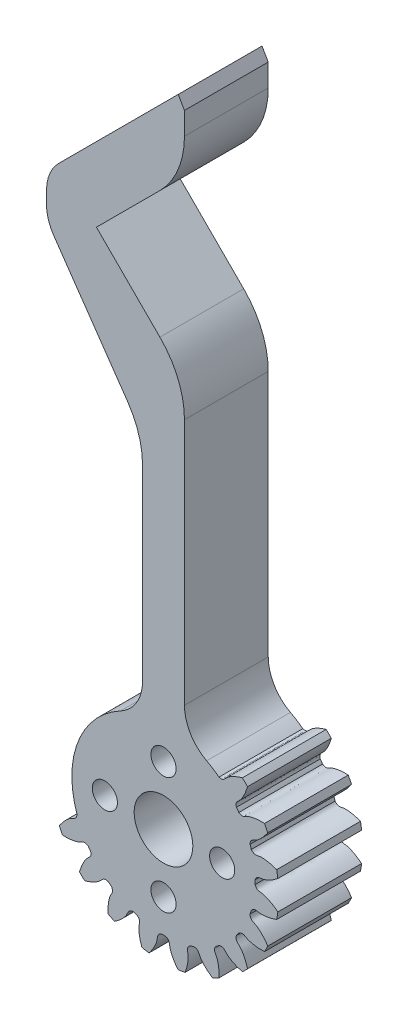
SolidWorks part; units mm, degrees
material "聚脂树脂"
ref_plane "前视基准面" through (0, 0, 0) normal (0, 0, 1) x (1, 0, 0)
ref_plane "上视基准面" through (0, 0, 0) normal (0, 1, 0) x (1, 0, 0)
ref_plane "右视基准面" through (0, 0, 0) normal (1, 0, 0) x (0, 0, -1)
other "Configuration Table"
sketch "草图1" plane through (0, 0, 0) normal (0, 0, 1) x (1, 0, 0)
  circle A0 centre (0, 0) radius 13.75
extrude "凸台-拉伸1" add sketch "草图1" along normal blind 10
ref_axis "基准轴1" through (0, 0, -1.5) along (0, 0, 1)
sketch "草图2" plane through (0, 0, 0) normal (0, 0, 1) x (1, 0, 0)
  line L0 (0, 0) -> (0, 13.75) construction
  circle A0 centre (0, 0) radius 13.75 construction
  arc A1 (0.2416, 10.9348) -> (-0.2416, 10.9348) centre (0, 0) ccw
  arc A2 (3.9764, 15.6228) -> (-3.9764, 15.6228) centre (0, 0) ccw
  spline S0 degree 3 poles (0.2416, 10.9348) (0.764, 11.1168) (0.6964, 11.4839) (0.7661, 11.8375) (0.7736, 11.8719) (0.7829, 11.9108) (0.7941, 11.954) (0.8075, 12.0015) (0.8231, 12.0532) (0.8413, 12.1091) (0.8621, 12.169) (0.8857, 12.2329) (0.9123, 12.3007) (0.9421, 12.3723) (0.9752, 12.4476) (1.0117, 12.5264) (1.0519, 12.6088) (1.0959, 12.6945) (1.1438, 12.7834) (1.1957, 12.8755) (1.2519, 12.9705) (1.3125, 13.0684) (1.3775, 13.1691) (1.4472, 13.2723) (1.5216, 13.3779) (1.601, 13.4858) (1.6853, 13.5958) (1.7747, 13.7078) (1.8694, 13.8216) (1.9693, 13.937) (2.0748, 14.0539) (2.1857, 14.1721) (2.3023, 14.2914) (2.4246, 14.4116) (2.5527, 14.5326) (2.6866, 14.6542) (2.8265, 14.7761) (2.9725, 14.8983) (3.1245, 15.0204) (3.2826, 15.1424) (3.4469, 15.2639) (3.6768, 15.427) (3.8549, 15.5454) (3.9764, 15.6228) knots 0 0 0 0 0.165916 0.170906 0.176664 0.183189 0.190482 0.198542 0.207371 0.216967 0.22733 0.238462 0.250361 0.263027 0.276462 0.290664 0.305634 0.321371 0.337876 0.355149 0.37319 0.391998 0.411574 0.431917 0.453028 0.474907 0.497554 0.520968 0.54515 0.570099 0.595817 0.622302 0.649554 0.677575 0.706363 0.735918 0.766242 0.797333 0.829191 0.861818 0.895212 0.929373 1 1 1 1
  spline S1 degree 3 poles (-0.2416, 10.9348) (-0.764, 11.1168) (-0.6964, 11.4839) (-0.7661, 11.8375) (-0.7736, 11.8719) (-0.7829, 11.9108) (-0.7941, 11.954) (-0.8075, 12.0015) (-0.8231, 12.0532) (-0.8413, 12.1091) (-0.8621, 12.169) (-0.8857, 12.2329) (-0.9123, 12.3007) (-0.9421, 12.3723) (-0.9752, 12.4476) (-1.0117, 12.5264) (-1.0519, 12.6088) (-1.0959, 12.6945) (-1.1438, 12.7834) (-1.1957, 12.8755) (-1.2519, 12.9705) (-1.3125, 13.0684) (-1.3775, 13.1691) (-1.4472, 13.2723) (-1.5216, 13.3779) (-1.601, 13.4858) (-1.6853, 13.5958) (-1.7747, 13.7078) (-1.8694, 13.8216) (-1.9693, 13.937) (-2.0748, 14.0539) (-2.1857, 14.1721) (-2.3023, 14.2914) (-2.4246, 14.4116) (-2.5527, 14.5326) (-2.6866, 14.6542) (-2.8265, 14.7761) (-2.9725, 14.8983) (-3.1245, 15.0204) (-3.2826, 15.1424) (-3.4469, 15.2639) (-3.6768, 15.427) (-3.8549, 15.5454) (-3.9764, 15.6228) knots 0 0 0 0 0.165916 0.170906 0.176664 0.183189 0.190482 0.198542 0.207371 0.216967 0.22733 0.238462 0.250361 0.263027 0.276462 0.290664 0.305634 0.321371 0.337876 0.355149 0.37319 0.391998 0.411574 0.431917 0.453028 0.474907 0.497554 0.520968 0.54515 0.570099 0.595817 0.622302 0.649554 0.677575 0.706363 0.735918 0.766242 0.797333 0.829191 0.861818 0.895212 0.929373 1 1 1 1
extrude "切除-拉伸1" cut sketch "草图2" along normal through all
pattern_circular "阵列(圆周)1" count 20 every 18 about axis through (0, 0, -1.5) along (0, 0, 1) of "切除-拉伸1"
sketch "草图6" plane through (0, 0, 0) normal (0, 0, -1) x (-1, 0, 0)
  line L0 (0, 0) -> (0, 65.9124) construction
  line L1 (0, 0) -> (39.45, 0) construction
  line L2 (0, 0) -> (-30.8379, 0) construction
  line L3 (-12.5, 0) -> (-12.5, 56.4778) construction
  line L4 (2.5, 0) -> (2.5, 36.4026)
  line L5 (-2.5, 0) -> (-2.5, 36.4026)
  line L6 (-2.5, 36.4026) -> (-2.5, 75.5405)
  line L7 (-2.5, 75.5405) -> (-12.5, 58.22) construction
  line L8 (-2.5, 75.5405) -> (6.3052, 90.7916) construction
  line L9 (-2.5, 75.5405) -> (0.7382, 81.1492)
  line L10 (-2.5, 0) -> (2.5, 0)
  line L11 (-5.8534, 12.4419) -> (-2.5, 14.378)
  line L12 (5.8534, 12.4419) -> (2.5, 14.378)
  line L17 (-1.7564, 76.8284) -> (13.7999, 61.272)
  line L18 (-12.5, 37.7139) -> (8.0061, 58.22)
  line L19 (-12.5, 37.7139) -> (-33.0061, 58.22)
  line L20 (-33.0061, 58.22) -> (-12.5, 78.7261)
  line L21 (8.0061, 58.22) -> (-12.5, 78.7261)
  line L22 (2.5, 36.4026) -> (2.5, 39.485)
  line L23 (6.7561, 59.47) -> (8.7561, 59.47)
  line L24 (8.7561, 59.47) -> (8.7561, 56.97)
  line L25 (8.7561, 56.97) -> (6.7561, 56.97)
  line L26 (2.5, 39.485) -> (13.8775, 55.9335)
  circle A0 centre (0, 0) radius 12.5 construction
  circle A1 centre (-12.5, 58.22) radius 24 construction
  circle A2 centre (-12.5, 58.22) radius 26.4764 construction
  arc A3 (0.7382, 81.1492) -> (2.5, 36.4026) centre (-12.5, 58.22) cw
  arc A4 (-0.5, 79.0046) -> (-2.5, 36.4026) centre (-12.5, 58.22) cw
  circle A5 centre (-12.5, 58.22) radius 20.5061 construction
  spline S0 degree 3 poles (5837.5155, 3864.2395) (-49.1578, -29.6908) (-0.8621, 4.7049) (-4.3931, 11.033) (-4.4189, 11.076) (-4.4589, 11.1387) (-4.5098, 11.2131) (-4.5827, 11.3111) (-4.6712, 11.4208) (-4.7765, 11.541) (-4.8994, 11.6706) (-5.0408, 11.8083) (-5.2016, 11.9528) (-5.3825, 12.1027) (-5.5474, 12.2287) (-5.6899, 12.331) (-35.2983, 32.707) (-218.0349, -174.3414) (6459.0271, 2694.747) knots -3.368657 -3.368657 -3.368657 -3.368657 0.165916 0.170906 0.183189 0.190482 0.207371 0.22733 0.250361 0.276462 0.305634 0.337876 0.37319 0.411574 0.453028 0.474907 0.497554 18.069832 18.069832 18.069832 18.069832 only from (-3.6089, 10.325) to (-5.8534, 12.4419) construction
  spline S1 degree 3 poles (-2.5, 10.5572) (-4.142, 10.0012) (-4.1368, 10.5737) (-4.3931, 11.033) (-4.4189, 11.076) (-4.4589, 11.1387) (-4.5098, 11.2131) (-4.5827, 11.3111) (-4.6712, 11.4208) (-4.7765, 11.541) (-4.8994, 11.6706) (-5.0408, 11.8083) (-5.2016, 11.9528) (-5.3825, 12.1027) (-5.5842, 12.2567) (-5.7442, 12.3691) (-5.8366, 12.4308) (-5.8534, 12.4419) knots -0.074607 -0.074607 -0.074607 -0.074607 0.165916 0.170906 0.183189 0.190482 0.207371 0.22733 0.250361 0.276462 0.305634 0.337876 0.37319 0.411574 0.453028 0.497554 0.507432 0.507432 0.507432 0.507432
  spline S2 degree 3 poles (-5837.5155, 3864.2395) (49.1578, -29.6908) (0.8621, 4.7049) (4.3931, 11.033) (4.4189, 11.076) (4.4589, 11.1387) (4.5098, 11.2131) (4.5827, 11.3111) (4.6712, 11.4208) (4.7765, 11.541) (4.8994, 11.6706) (5.0408, 11.8083) (5.2016, 11.9528) (5.3825, 12.1027) (5.5474, 12.2287) (5.6899, 12.331) (35.2983, 32.707) (218.0349, -174.3414) (-6459.0271, 2694.747) knots -2.876089 -2.876089 -2.876089 -2.876089 0.658484 0.663474 0.675757 0.68305 0.699939 0.719899 0.742929 0.76903 0.798202 0.830445 0.865758 0.904142 0.945597 0.967475 0.990122 18.5624 18.5624 18.5624 18.5624 only from (3.6089, 10.325) to (5.8534, 12.4419) construction
  spline S3 degree 3 poles (2.5, 10.5572) (4.142, 10.0012) (4.1368, 10.5737) (4.3931, 11.033) (4.4189, 11.076) (4.4589, 11.1387) (4.5098, 11.2131) (4.5827, 11.3111) (4.6712, 11.4208) (4.7765, 11.541) (4.8994, 11.6706) (5.0408, 11.8083) (5.2016, 11.9528) (5.3825, 12.1027) (5.5842, 12.2567) (5.7442, 12.3691) (5.8366, 12.4308) (5.8534, 12.4419) knots 0.417962 0.417962 0.417962 0.417962 0.658484 0.663474 0.675757 0.68305 0.699939 0.719899 0.742929 0.76903 0.798202 0.830445 0.865758 0.904142 0.945597 0.990122 1 1 1 1
  dimension "D1" = 25
  dimension "D4" = 48
  dimension "D5" = 30
  dimension "D8" = 29
  dimension "D9" = 22
  dimension "D13" = 20
  dimension "D2" = 5
  dimension "D3" = 58.22
  dimension "D6" = 60
  dimension "D7" = 60
  dimension "D10" = 2
  dimension "D11" = 2
  dimension "D12" = 2.5
extrude "凸台-拉伸2" add sketch "草图6" against normal blind 10 contours A3 L9 L6 L5 L10 L4 | S1 L5 L11 | L4 S3 L12 | A4 L9 L6 L21 L18 | L17 A4 L26 A3 | L25 L24 L23 L21 L18 region at (-0.0338, 18.9116, 0) region at (-3.6667, 12.1825, 0) region at (3.6667, 12.1825, 0) region at (0.1299, 38.1544, 0) region at (-12.3775, 58.1016, 0) region at (-8.0212, 58.22, 0)
ref_plane "基准面1" through (12.5, 0, 0) normal (1, 0, 0) x (0, 0, -1)
sketch "草图4" plane through (0, 0, 10) normal (0, 0, 1) x (1, 0, 0)
  line L0 (0, 0) -> (0, 14.4175) construction
  line L1 (0, 0) -> (19.7904, 0) construction
  circle A0 centre (0, 0) radius 9
  circle A1 centre (0, 0) radius 3.5
  circle A2 centre (0, 7) radius 1.5
  circle A3 centre (7, 0) radius 1.5
  circle A4 centre (0, -7) radius 1.5
  circle A5 centre (-7, 0) radius 1.5
  dimension "D1" = 18
  dimension "D2" = 7
  dimension "D3" = 3
  dimension "D4" = 3
  dimension "D5" = 7
  dimension "D6" = 7
extrude "切除-拉伸2" cut sketch "草图4" against normal blind 20 contours A1 | A5 | A2 | A3 | A4
ref_plane "基准面2" through (0, 0, 9) normal (0, 0, 1) x (1, 0, 0)
sketch "草图17" plane through (0, 0, 10) normal (0, 0, 1) x (1, 0, 0)
  line L0 (0, 0) -> (-6.6228, 8.7044)
  line L1 (-6.6228, 8.7044) -> (-11.857, 15.5837)
  line L2 (0, 0) -> (-10.325, -3.6089)
  line L3 (-10.325, -3.6089) -> (-17.9409, -6.2709)
  circle A0 centre (0, 0) radius 10.9375
  arc A1 (-6.2318, 8.9885) -> (-6.6228, 8.7044) centre (0, 0) ccw construction
  circle A2 centre (0, 0) radius 17.5
  dimension "D1" = 35
extrude "切除-拉伸5" cut sketch "草图17" against normal blind 10 contours L1 A2 L3 A0 region at (-12.9643, 3.8979, 10)
sketch "草图20" plane through (0, 0, 0) normal (0, 0, -1) x (-1, 0, 0)
  line L0 (-2.5, 14.378) -> (-2.5, 10.648)
  line L1 (2.5, 14.378) -> (2.5, 10.648)
  line L2 (5.8534, 12.4419) -> (2.5, 14.378) construction
  line L3 (-5.8534, 12.4419) -> (-2.5, 14.378) construction
  line L4 (5.8534, 12.4419) -> (2.5, 14.378)
  line L5 (-5.8534, 12.4419) -> (-2.5, 14.378)
  circle A0 centre (0, 0) radius 10.9375
  arc A1 (10.325, -3.6089) -> (6.2318, 8.9885) centre (0, 0) ccw construction
  arc A2 (6.6252, 12.0486) -> (5.8534, 12.4419) centre (0, 0) ccw construction
  arc A3 (-5.8534, 12.4419) -> (-6.6252, 12.0486) centre (0, 0) ccw construction
  arc A4 (6.6252, 12.0486) -> (5.8534, 12.4419) centre (0, 0) ccw
  arc A5 (-5.8534, 12.4419) -> (-6.6252, 12.0486) centre (0, 0) ccw
  spline S0 degree 3 poles (1876.625, -698.848) (-20.9969, 12.4766) (4.3246, 5.6774) (6.3437, 10.0391) (6.3633, 10.0853) (6.3905, 10.1545) (6.4208, 10.2394) (6.4573, 10.356) (6.4939, 10.4921) (6.5293, 10.6479) (6.5619, 10.8235) (6.5902, 11.0188) (6.6126, 11.2338) (6.6276, 11.4683) (6.6325, 11.6758) (6.6315, 11.8512) (6.0134, 36.0214) (-118.4428, 55.7409) (1694.3797, -1060.7669) knots -2.172632 -2.172632 -2.172632 -2.172632 0.165916 0.170906 0.183189 0.190482 0.207371 0.22733 0.250361 0.276462 0.305634 0.337876 0.37319 0.411574 0.453028 0.474907 0.497554 12.30377 12.30377 12.30377 12.30377 only from (6.2318, 8.9885) to (6.6252, 12.0486) construction
  spline S1 degree 3 poles (-1876.625, -698.848) (20.9969, 12.4766) (-4.3246, 5.6774) (-6.3437, 10.0391) (-6.3633, 10.0853) (-6.3905, 10.1545) (-6.4208, 10.2394) (-6.4573, 10.356) (-6.4939, 10.4921) (-6.5293, 10.6479) (-6.5619, 10.8235) (-6.5902, 11.0188) (-6.6126, 11.2338) (-6.6276, 11.4683) (-6.6325, 11.6758) (-6.6315, 11.8512) (-6.0134, 36.0214) (118.4428, 55.7409) (-1694.3797, -1060.7669) knots -1.680063 -1.680063 -1.680063 -1.680063 0.658484 0.663474 0.675757 0.68305 0.699939 0.719899 0.742929 0.76903 0.798202 0.830445 0.865758 0.904142 0.945597 0.967475 0.990122 12.796339 12.796339 12.796339 12.796339 only from (-6.2318, 8.9885) to (-6.6252, 12.0486) construction
  spline S2 degree 3 poles (6.2318, 8.9885) (5.9162, 9.4428) (6.1867, 9.7) (6.3437, 10.0391) (6.3633, 10.0853) (6.3905, 10.1545) (6.4208, 10.2394) (6.4573, 10.356) (6.4939, 10.4921) (6.5293, 10.6479) (6.5619, 10.8235) (6.5902, 11.0188) (6.6126, 11.2338) (6.6276, 11.4683) (6.6336, 11.722) (6.6305, 11.9176) (6.6261, 12.0285) (6.6252, 12.0486) knots 0 0 0 0 0.165916 0.170906 0.183189 0.190482 0.207371 0.22733 0.250361 0.276462 0.305634 0.337876 0.37319 0.411574 0.453028 0.497554 0.507432 0.507432 0.507432 0.507432
  spline S3 degree 3 poles (-6.2318, 8.9885) (-5.9162, 9.4428) (-6.1867, 9.7) (-6.3437, 10.0391) (-6.3633, 10.0853) (-6.3905, 10.1545) (-6.4208, 10.2394) (-6.4573, 10.356) (-6.4939, 10.4921) (-6.5293, 10.6479) (-6.5619, 10.8235) (-6.5902, 11.0188) (-6.6126, 11.2338) (-6.6276, 11.4683) (-6.6336, 11.722) (-6.6305, 11.9176) (-6.6261, 12.0285) (-6.6252, 12.0486) knots 0.492568 0.492568 0.492568 0.492568 0.658484 0.663474 0.675757 0.68305 0.699939 0.719899 0.742929 0.76903 0.798202 0.830445 0.865758 0.904142 0.945597 0.990122 1 1 1 1
extrude "切除-拉伸7" cut sketch "草图20" against normal blind 10 contours S3 A0 L0 L5 A5 | A0 S2 A4 L4 L1 region at (4.4205, 11.6437, 0) region at (-4.4205, 11.6437, 0)
fillet "圆角7" radius 5 2 edges at (-2.5, 10.648, 5) (2.5, 10.648, 5)
fillet "圆角8" radius 10 2 edges at (2.5, 47.7139, 5) (2.5, 68.7261, 5)
fillet "圆角15" radius 5 2 edges at (-13.7999, 61.272, 5) (-13.8775, 55.9335, 5)
fillet "圆角16" radius 10 1 edges at (-2.5, 39.485, 5)
